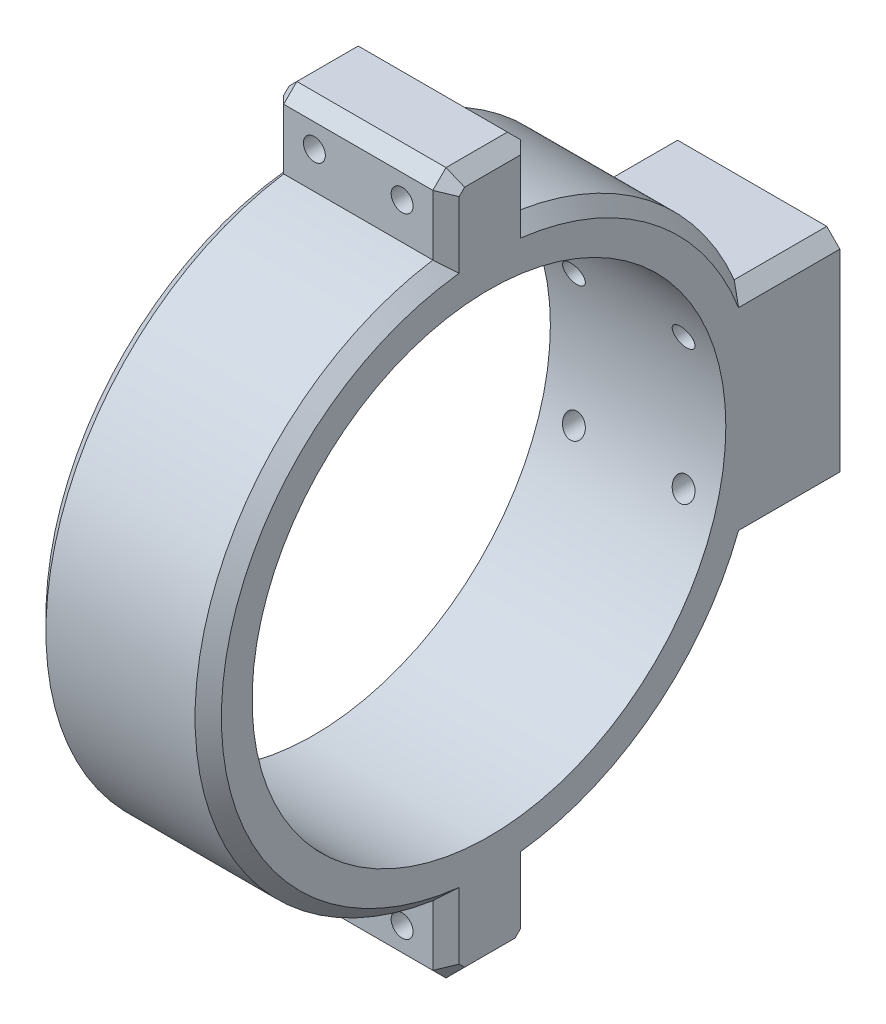
SolidWorks part; units mm, degrees
ref_plane "前视基准面" through (0, 0, 0) normal (0, 0, 1) x (1, 0, 0)
ref_plane "上视基准面" through (0, 0, 0) normal (0, 1, 0) x (1, 0, 0)
ref_plane "右视基准面" through (0, 0, 0) normal (1, 0, 0) x (0, 0, -1)
sketch "草图2" plane through (0, 0, 0) normal (1, 0, 0) x (0, 0, -1)
  circle A0 centre (0, 0) radius 32
  dimension "D1" = 64
extrude "凸台-拉伸1" add sketch "草图2" along normal blind 20
sketch "草图3" plane through (20, 0, 0) normal (1, 0, 0) x (0, 0, -1)
  circle A0 centre (0, 0) radius 27
  dimension "D1" = 54
extrude "切除-拉伸1" cut sketch "草图3" against normal through all
sketch "草图4" plane through (20, 0, 0) normal (1, 0, 0) x (0, 0, -1)
  line L1 (23.9322, 12.5) -> (40, 12.5)
  line L2 (23.9322, 12.5) -> (23.9322, -12.5)
  line L3 (23.9322, -12.5) -> (40, -12.5)
  line L4 (40, 12.5) -> (40, -12.5)
  line L5 (23.9322, 12.5) -> (40, -12.5) construction
  line L6 (23.9322, -12.5) -> (40, 12.5) construction
  circle A0 centre (0, 0) radius 27 construction
  circle A1 centre (0, 0) radius 32 construction
  point P0 (31.9661, 0)
  dimension "D1" = 40
  dimension "D2" = 25
extrude "凸台-拉伸2" add sketch "草图4" against normal blind 20
sketch "草图5" plane through (20, 0, 0) normal (1, 0, 0) x (0, 0, -1)
  circle A0 centre (0, 0) radius 27
  dimension "D1" = 54
extrude "切除-拉伸2" cut sketch "草图5" against normal through all
sketch "草图8" plane through (20, 0, 0) normal (1, 0, 0) x (0, 0, -1)
  line L0 (-32, 0) -> (40, 0) construction
  line L1 (5.0998, 26.5516) -> (-4.9002, 26.5516)
  line L2 (5.0998, 26.5516) -> (5.0998, 40)
  line L3 (5.0998, 40) -> (-4.9002, 40)
  line L4 (-4.9002, 26.5516) -> (-4.9002, 40)
  line L5 (5.0998, 26.5516) -> (-4.9002, 40) construction
  line L6 (5.0998, 40) -> (-4.9002, 26.5516) construction
  line L7 (40, -12.5) -> (40, 12.5) construction
  line L8 (5.0998, -40) -> (-4.9002, -40)
  line L9 (-4.9002, -26.5516) -> (-4.9002, -40)
  line L10 (5.0998, -26.5516) -> (-4.9002, -26.5516)
  line L11 (5.0998, -26.5516) -> (5.0998, -40)
  line L12 (0.0998, 50.6797) -> (0.0998, -34.5244) construction
  circle A0 centre (0, 0) radius 27 construction
  circle A1 centre (0, 0) radius 32 construction
  circle A2 centre (0, 0) radius 32 construction
  point P0 (0.0998, 33.2758)
  dimension "D1" = 10
  dimension "D2" = 40
extrude "凸台-拉伸4" add sketch "草图8" against normal up to surface (20 mm away) up to face at (0, 0, -19.3644)
sketch "草图9" plane through (0, 0, 4.9002) normal (0, 0, 1) x (1, 0, 0)
  line L0 (0, 35.8113) -> (20, 35.8113) construction
  line L1 (0, 40) -> (0, 31.6226) construction
  line L2 (20, 40) -> (20, 31.6226) construction
  line L3 (10, 40) -> (10, 31.6226) construction
  line L4 (0, 40) -> (20, 40) construction
  line L5 (20, 31.6226) -> (0, 31.6226) construction
  line L6 (0, 0) -> (28.5789, 0) construction
  circle A0 centre (5, 35.8113) radius 1.25
  circle A1 centre (15, 35.8113) radius 1.25
  circle A2 centre (15, -35.8113) radius 1.25
  circle A3 centre (5, -35.8113) radius 1.25
  dimension "D1" = 2.5
  dimension "D2" = 2.5
  dimension "D3" = 5
extrude "切除-拉伸4" cut sketch "草图9" against normal up to next
sketch "草图10" plane through (20, 0, 0) normal (1, 0, 0) x (0, 0, -1)
  circle A0 centre (0, 0) radius 27
  dimension "D1" = 54
extrude "切除-拉伸5" cut sketch "草图10" against normal through all
chamfer "倒角2" distance 1.5 angle 45 4 edges at (10, -40, 4.9002) (10, -40, -5.0998) (10, 40, -5.0998) (10, 40, 4.9002)
chamfer "倒角3" distance 1.5 angle 45 25 edges at (0, -25.1859, -19.74) (0, -35.0455, -5.0998) (0, -39.25, -4.3498) (0, -40, -0.0998) (0, -39.25, 4.1502) (0, -35.0613, 4.9002) (0, 25.1859, -19.74) (0, 35.0455, -5.0998) (0, 39.25, -4.3498) (0, 40, -0.0998) (0, 39.25, 4.1502) (0, 35.0613, 4.9002) (0, 0, 32) (20, 35.0455, -5.0998) (20, 25.1859, -19.74) (20, -25.1859, -19.74) (20, -35.0455, -5.0998) (20, -39.25, -4.3498) (20, -40, -0.0998) (20, -39.25, 4.1502) (20, -35.0613, 4.9002) (20, 40, -0.0998) (20, 39.25, 4.1502) (20, 35.0613, 4.9002) (20, 0, 32)
sketch "草图17" plane through (0, 0, -40) normal (0, 0, -1) x (-1, 0, 0)
  line L0 (-10, 12.5) -> (-10, -12.5) construction
  line L1 (0, 12.5) -> (-20, 12.5) construction
  line L2 (0, -12.5) -> (-20, -12.5) construction
  line L3 (-20, 0) -> (0, 0) construction
  line L4 (-20, -12.5) -> (-20, 12.5) construction
  line L5 (0, -12.5) -> (0, 12.5) construction
  circle A0 centre (-16.25, 7.5) radius 1.25
  circle A1 centre (-3.75, 7.5) radius 1.25
  circle A2 centre (-3.75, -7.5) radius 1.25
  circle A3 centre (-16.25, -7.5) radius 1.25
  point P20 (0, 0)
  point P21 (0, 0)
  point P22 (0, 0)
  dimension "D1" = 2.5
  dimension "D2" = 12.5
  dimension "D3" = 15
extrude "切除-拉伸11" cut sketch "草图17" against normal up to surface (14.0626 mm away) up to face at (0, 0, -27)
chamfer "倒角4" distance 1.5 angle 45 4 edges at (0, -12.5, -33.9104) (0, 12.5, -33.9104) (20, -12.5, -33.9104) (20, 12.5, -33.9104)
sketch "草图11" plane through (0, 0, 0) normal (0, 0, 1) x (1, 0, 0)
  line L1 (60.6516, -49.0819) -> (-27.9407, -49.0819)
  line L2 (60.6516, -49.0819) -> (60.6516, 47.2432)
  line L3 (60.6516, 47.2432) -> (-27.9407, 47.2432)
  line L4 (-27.9407, -49.0819) -> (-27.9407, 47.2432)
  line L5 (60.6516, -49.0819) -> (-27.9407, 47.2432) construction
  line L6 (60.6516, 47.2432) -> (-27.9407, -49.0819) construction
  point P0 (16.3554, -0.9194)
extrude "切除-拉伸9" [suppressed] cut sketch "草图11" against normal through all
sketch "草图16" [suppressed] plane through (0, 0, 0) normal (0, 0, -1) x (-1, 0, 0)
  circle A0 centre (-15, 35.8113) radius 1.5
  circle A1 centre (-5, 35.8113) radius 1.5
  circle A2 centre (-5, -35.8113) radius 1.5
  circle A3 centre (-15, -35.8113) radius 1.5
  dimension "D1" = 3
extrude "切除-拉伸10" [suppressed] cut sketch "草图16" against normal up to next
